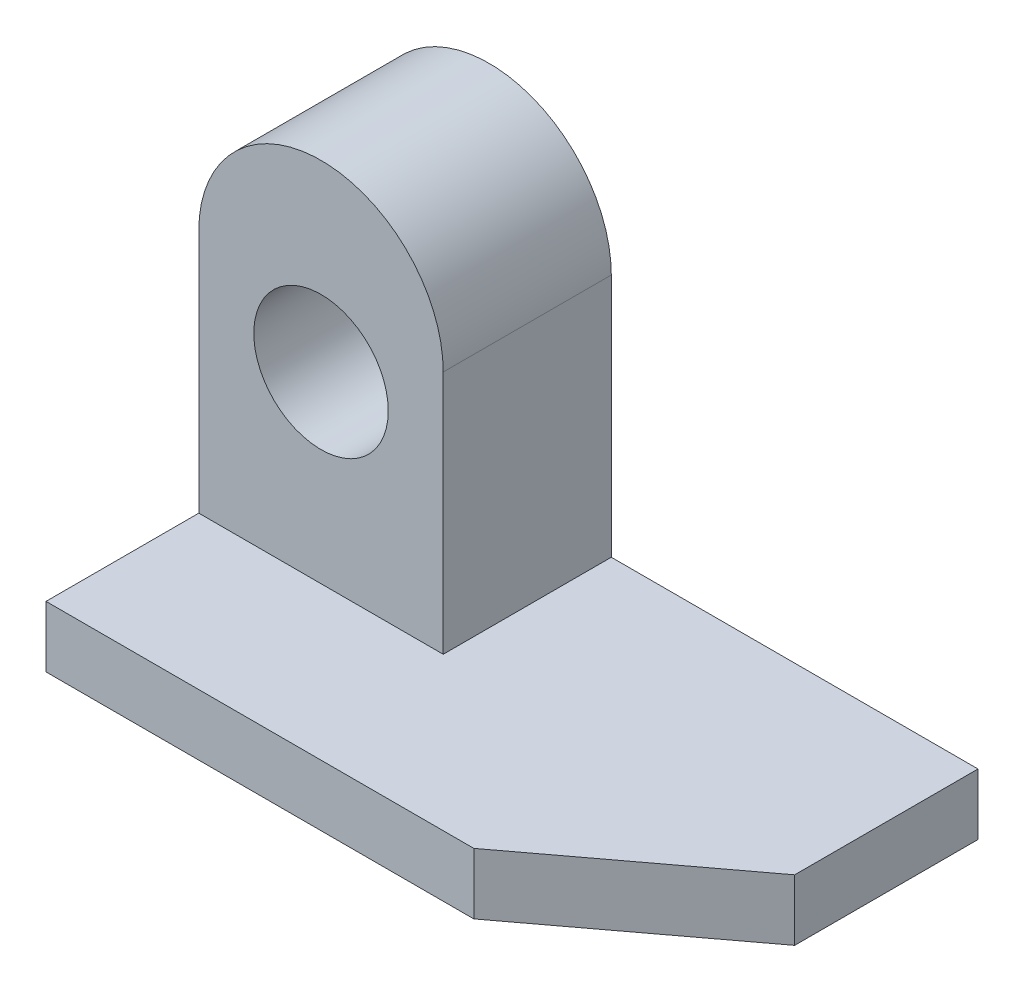
SolidWorks part; units mm, degrees
ref_plane "Front Plane" through (0, 0, 0) normal (0, 0, 1) x (1, 0, 0)
ref_plane "Top Plane" through (0, 0, 0) normal (0, 1, 0) x (1, 0, 0)
ref_plane "Right Plane" through (0, 0, 0) normal (1, 0, 0) x (0, 0, -1)
sketch "Sketch1" plane through (0, 0, 0) normal (0, 1, 0) x (1, 0, 0)
  line L0 (-200, 60) -> (0, 60)
  line L1 (0, 60) -> (0, 0)
  line L2 (0, 0) -> (-60, -45)
  line L3 (-60, -45) -> (-200, -45)
  line L4 (-200, -45) -> (-200, 60)
  point P2 (0, 0)
  dimension "D1" = 105
  dimension "D2" = 60
  dimension "D3" = 140
  dimension "D4" = 200
extrude "Boss-Extrude1" add sketch "Sketch1" along normal blind 20
sketch "Sketch4" plane through (0, 20, 0) normal (0, 1, 0) x (1, 0, 0)
  line L0 (-200, -45) -> (-60, -45) construction
  line L1 (-200, 60) -> (-120, 60)
  line L2 (-200, 60) -> (-200, 5)
  line L3 (-200, 5) -> (-120, 5)
  line L4 (-120, 60) -> (-120, 5)
  dimension "D1" = 50
  dimension "D2" = 80
extrude "Boss-Extrude3" add sketch "Sketch4" along normal blind 120
fillet "Fillet2" 2 edges at (-120, 140, -32.5) (-200, 140, -32.5) type full round first side face at (-120, 80, -32.5) second side face at (-200, 53.3333, -6.6667) middle face at (-160, 140, -32.5)
sketch "Sketch5" plane through (0, 0, -5) normal (0, 0, 1) x (1, 0, 0)
  line L0 (-120, 100) -> (-120, 20) construction
  circle A0 centre (-160, 80) radius 22
  dimension "D1" = 44
  dimension "D2" = 60
  dimension "D3" = 40
extrude "Cut-Extrude1" cut sketch "Sketch5" against normal blind 120
